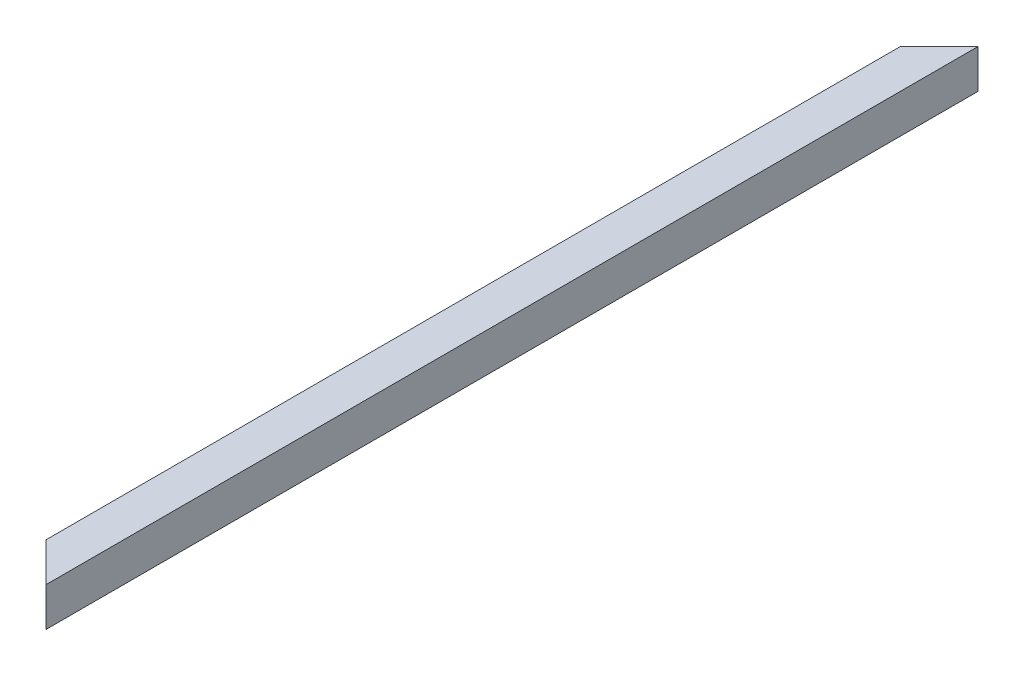
SolidWorks part; units mm, degrees
ref_plane "Front Plane" through (0, 0, 0) normal (0, 0, 1) x (1, 0, 0)
ref_plane "Top Plane" through (0, 0, 0) normal (0, 1, 0) x (1, 0, 0)
ref_plane "Right Plane" through (0, 0, 0) normal (1, 0, 0) x (0, 0, -1)
sketch "Sketch1" plane through (0, 0, 0) normal (0, 0, 1) x (1, 0, 0)
  line L0 (0, 0) -> (0, -25.4)
  line L9 (0, -25.4) -> (-6.35, -25.4)
  line L10 (-6.35, -25.4) -> (-6.35, -6.35)
  line L11 (-6.35, -6.35) -> (-25.4, -6.35)
  line L12 (-25.4, -6.35) -> (-25.4, 0)
  line L13 (-25.4, 0) -> (0, 0)
  dimension "D1" = 25.4
  dimension "D2" = 25.4
  dimension "D3" = 6.35
extrude "Boss-Extrude1" add sketch "Sketch1" along normal blind 609.6
chamfer "Chamfer1" distance 25.4 angle 45 2 edges at (-25.4, -3.175, 0) (-25.4, -3.175, 609.6)
